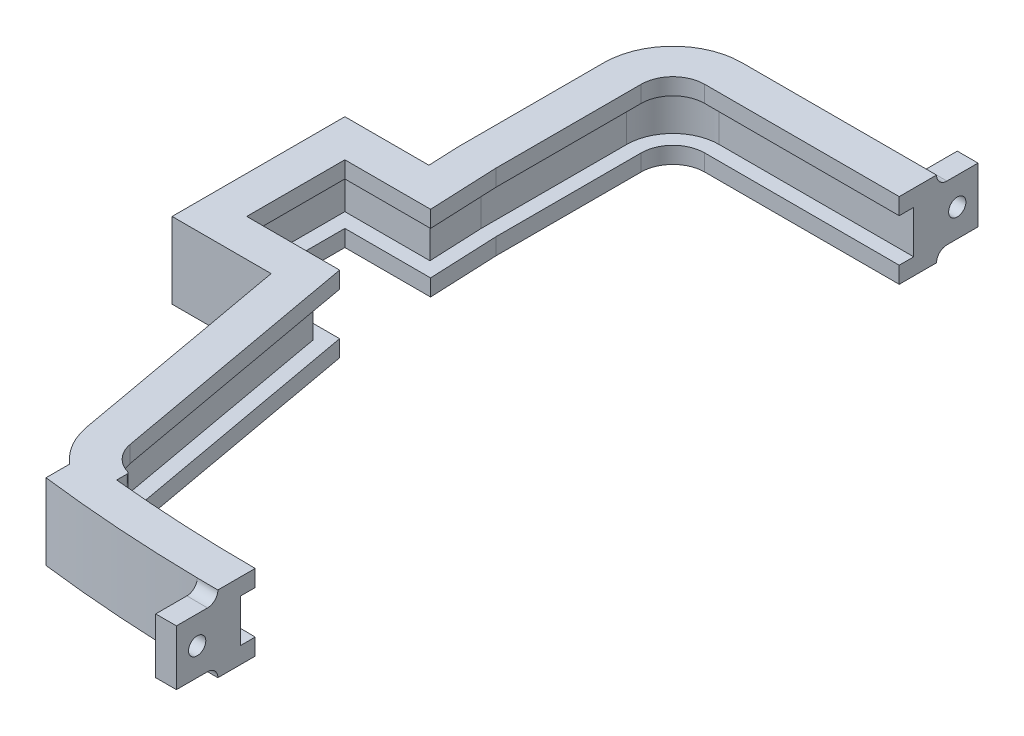
SolidWorks part; units mm, degrees
ref_plane "Front Plane" through (0, 0, 0) normal (0, 0, 1) x (1, 0, 0)
ref_plane "Top Plane" through (0, 0, 0) normal (0, 1, 0) x (1, 0, 0)
ref_plane "Right Plane" through (0, 0, 0) normal (1, 0, 0) x (0, 0, -1)
sketch "Sketch2" plane through (0, 0, 0) normal (0, 1, 0) x (1, 0, 0)
  line L0 (-32.15, 40) -> (-32.15, 19)
  line L1 (-28.15, 44) -> (28.15, 44)
  line L2 (32.15, 40) -> (32.15, 19)
  line L3 (-32.15, 19) -> (-31.6916, 8.5)
  line L6 (-28.15, 50) -> (28.15, 50)
  line L8 (38.15, 40) -> (38.15, 18.8691)
  line L10 (37.9592, 14.5) -> (38.15, 18.8691)
  line L11 (37.9592, 14.5) -> (50.124, 14.5)
  line L12 (50.124, -10.5) -> (50.124, 14.5)
  line L13 (35.7934, -10.5) -> (50.124, -10.5)
  line L14 (35.7934, -10.5) -> (29.9042, -43.0677)
  line L15 (26.5, -52.373) -> (26.5, -48.9417)
  line L16 (-26.5, -52.373) -> (-26.5, -48.9417)
  line L17 (-29.9042, -43.0677) -> (-35.7934, -10.5)
  line L18 (-50.124, -10.5) -> (-35.7934, -10.5)
  line L19 (-50.124, -10.5) -> (-50.124, 14.5)
  line L20 (-50.124, 14.5) -> (-37.9592, 14.5)
  line L21 (-38.15, 18.8691) -> (-37.9592, 14.5)
  line L22 (-38.15, 40) -> (-38.15, 18.8691)
  line L23 (-28.15, 46.7) -> (28.15, 46.7)
  line L24 (-50, 2) -> (50, 2) construction
  line L25 (-44.124, -4.5) -> (-30.7811, -4.5)
  line L26 (30.7811, -4.5) -> (44.124, -4.5)
  line L28 (31.6916, 8.5) -> (44.124, 8.5)
  line L29 (44.124, -4.5) -> (44.124, 8.5)
  line L30 (34.85, 40) -> (34.85, 18.9411)
  line L31 (-20.5, -47) -> (-20.5, -46.0775)
  line L32 (-44.124, -4.5) -> (-44.124, 8.5)
  line L33 (-44.124, 8.5) -> (-31.6916, 8.5)
  line L35 (-20.5, -47) -> (20.5, -47) construction
  line L36 (34.512, 11.2) -> (34.85, 18.9411)
  line L38 (31.6916, 8.5) -> (32.15, 19)
  line L39 (34.512, 11.2) -> (46.824, 11.2)
  line L40 (46.824, -7.2) -> (46.824, 11.2)
  line L41 (33.0366, -7.2) -> (46.824, -7.2)
  line L42 (33.0366, -7.2) -> (26.6569, -42.4804)
  line L43 (23.2, -49.4347) -> (23.2, -47.2089)
  line L44 (-23.2, -49.4347) -> (-23.2, -47.2089)
  line L45 (-26.6569, -42.4804) -> (-33.0366, -7.2)
  line L46 (-46.824, -7.2) -> (-33.0366, -7.2)
  line L47 (-46.824, -7.2) -> (-46.824, 11.2)
  line L48 (-46.824, 11.2) -> (-34.512, 11.2)
  line L49 (-34.85, 18.9411) -> (-34.512, 11.2)
  line L50 (-34.85, 40) -> (-34.85, 18.9411)
  line L51 (-24.5904, -42.1068) -> (-31.2823, -5.1)
  line L52 (-44.724, -5.1) -> (-31.2823, -5.1)
  line L53 (-44.724, -5.1) -> (-44.724, 9.1)
  line L54 (-44.724, 9.1) -> (-32.3183, 9.1)
  line L55 (-21.5547, -45) -> (21.5547, -45) construction
  line L56 (-32.75, 18.9869) -> (-32.3183, 9.1)
  line L57 (-24, -42) -> (24, -42) construction
  line L58 (30.7811, -4.5) -> (24, -42)
  line L59 (-24, -42) -> (-30.7811, -4.5)
  line L60 (20.5, -47) -> (20.5, -46.0775)
  line L61 (-32.75, 40) -> (-32.75, 18.9869)
  line L62 (-28.15, 44.6) -> (28.15, 44.6)
  line L63 (32.75, 40) -> (32.75, 18.9869)
  line L64 (32.3183, 9.1) -> (32.75, 18.9869)
  line L65 (32.3183, 9.1) -> (44.724, 9.1)
  line L66 (44.724, -5.1) -> (44.724, 9.1)
  line L67 (31.2823, -5.1) -> (44.724, -5.1)
  line L68 (31.2823, -5.1) -> (24.5904, -42.1068)
  line L69 (21.1, -47.5435) -> (21.1, -46.0775)
  line L70 (-21.1, -47.5435) -> (-21.1, -46.0775)
  arc A2 (-28.15, 44) -> (-32.15, 40) centre (-28.15, 40) ccw
  arc A3 (32.15, 40) -> (28.15, 44) centre (28.15, 40) ccw
  arc A10 (38.15, 40) -> (28.15, 50) centre (28.15, 40) ccw
  arc A11 (29.9042, -43.0677) -> (26.5, -48.9417) centre (20.0638, -41.2882) cw
  arc A12 (26.5, -48.9417) -> (26.5, -48.9417) centre (26.5, -48.9417) cw
  arc A13 (-26.5, -52.373) -> (26.5, -52.373) centre (0, 162.625) ccw
  arc A14 (-26.5, -48.9417) -> (-26.5, -48.9417) centre (-26.5, -48.9417) ccw
  arc A15 (-29.9042, -43.0677) -> (-26.5, -48.9417) centre (-20.0638, -41.2882) ccw
  arc A16 (-28.15, 50) -> (-38.15, 40) centre (-28.15, 40) ccw
  arc A17 (34.85, 40) -> (28.15, 46.7) centre (28.15, 40) ccw
  arc A18 (26.6569, -42.4804) -> (23.2, -47.2089) centre (20.0638, -41.2882) cw
  arc A19 (23.2, -47.2089) -> (23.2, -47.2089) centre (23.2, -47.2089) cw
  arc A20 (-23.2, -49.4347) -> (23.2, -49.4347) centre (0, 162.625) ccw
  arc A21 (-23.2, -47.2089) -> (-23.2, -47.2089) centre (-23.2, -47.2089) ccw
  arc A22 (-20.5, -47) -> (20.5, -47) centre (0, 162.625) ccw
  arc A23 (-20.5, -46.0775) -> (-21.2128, -45.1197) centre (-21.5, -46.0775) ccw
  arc A24 (-24, -42) -> (-21.2128, -45.1197) centre (-20.0638, -41.2882) ccw
  arc A25 (24, -42) -> (21.2128, -45.1197) centre (20.0638, -41.2882) cw
  arc A26 (20.5, -46.0775) -> (21.2128, -45.1197) centre (21.5, -46.0775) cw
  arc A27 (-26.6569, -42.4804) -> (-23.2, -47.2089) centre (-20.0638, -41.2882) ccw
  arc A28 (-28.15, 46.7) -> (-34.85, 40) centre (-28.15, 40) ccw
  arc A29 (-28.15, 44.6) -> (-32.75, 40) centre (-28.15, 40) ccw
  arc A30 (32.75, 40) -> (28.15, 44.6) centre (28.15, 40) ccw
  arc A31 (24.5904, -42.1068) -> (21.3851, -45.6944) centre (20.0638, -41.2882) cw
  arc A32 (21.1, -46.0775) -> (21.3851, -45.6944) centre (21.5, -46.0775) cw
  arc A33 (-21.1, -47.5435) -> (21.1, -47.5435) centre (0, 162.625) ccw
  arc A34 (-21.1, -46.0775) -> (-21.3851, -45.6944) centre (-21.5, -46.0775) ccw
  arc A35 (-24.5904, -42.1068) -> (-21.3851, -45.6944) centre (-20.0638, -41.2882) ccw
  point P0 (0, 0)
  point P1 (-29.7948, -34.9429)
  point P3 (29.7948, -34.9429)
  point P26 (0, -48)
  point P34 (0, 2)
  point P43 (0, -48)
  point P80 (0, -2)
  point P103 (0, -47)
  point P104 (0, -42)
  dimension "D6" = 177.5
  dimension "D7" = 12.4324
  dimension "D8" = 13
  dimension "D9" = 4
  dimension "D12" = 6.5
  dimension "D18" = 6.5
  dimension "D19" = 6
  dimension "D20" = 42
  dimension "D25" = 0.6
  dimension "D29" = 8
  dimension "D30" = 2
  dimension "D31" = 4
  dimension "D32" = 1
  dimension "D1" = 44
  dimension "D2" = 177.5
  dimension "D4" = 32.15
  dimension "D5" = 32.15
  dimension "D10" = 21
  dimension "D11" = 21
  dimension "D13" = 42
  dimension "D14" = 2
  dimension "D15" = 100.25
  dimension "D16" = 13
  dimension "D17" = 100.25
  dimension "D21" = 100
  dimension "D22" = 48
  dimension "D23" = 12.4324
  dimension "D24" = 2.7
  dimension "D28" = 56.3
  dimension "D33" = 3
  dimension "D34" = 3
  dimension "D35" = 3.1197
  dimension "D36" = 0.9225
  dimension "D37" = 0
extrude "Boss-Extrude1" add sketch "Sketch2" against normal blind 4.5 contours L15 L42 L41 L40 L39 L23 L17 L16 A13 L6 L11 L12 L13 L14 | L23 A28 L50 L49 L48 L47 L46 L45 A27 L44 A20 L43 A18 L42 L41 L40 L39 L36 L30 A17 A35 L51 L52 L53 L54 L56 L61 A29 L62 A30 L63 L64 L65 L66 L67 L68 A31 A32 L69 A33 L70 A34 region at (0, 0, -48.5555) region at (0, 0, -45.3488)
extrude "Cut-Extrude3" cut sketch "Sketch2<6>" against normal blind 2.1 contours L23 A28 L50 L49 L48 L47 L46 L45 A27 L44 A20 L43 A18 L42 L41 L40 L39 L36 L30 A17 A35 L51 L52 L53 L54 L56 L61 A29 L62 A30 L63 L64 L65 L66 L67 L68 A31 A32 L69 A33 L70 A34 | L51 A35 A34 L70 A33 L69 A32 A31 L68 L67 L66 L65 L64 L63 A30 L62 A29 L61 L56 L54 L53 L52 A26 L60 A22 L31 A23 A24 L59 L25 L32 L33 L3 L0 A2 L1 A3 L2 L38 L28 L29 L26 L58 A25 region at (0, 0, -45.3488) region at (-27.8092, 0, 23.5804)
sketch "Sketch2<6>" plane through (0, 0, 0) normal (0, 1, 0) x (1, 0, 0) same geometry as "Sketch2"
extrude "Boss-Extrude3" add sketch "Sketch2<7>" along normal blind 6.5 contours L6 A16 L22 L21 L20 L19 L18 L17 A15 L16 A13 L15 A11 L14 L13 L12 L11 L10 L8 A10 A28 L23 A17 L30 L36 L39 L40 L41 L42 A18 L43 A20 L44 A27 L45 L46 L47 L48 L49 L50 | L23 A28 L50 L49 L48 L47 L46 L45 A27 L44 A20 L43 A18 L42 L41 L40 L39 L36 L30 A17 A35 L51 L52 L53 L54 L56 L61 A29 L62 A30 L63 L64 L65 L66 L67 L68 A31 A32 L69 A33 L70 A34 region at (0, 0, -48.5555) region at (0, 0, -45.3488)
sketch "Sketch2<7>" plane through (0, 0, 0) normal (0, 1, 0) x (1, 0, 0) same geometry as "Sketch2"
extrude "Cut-Extrude4" cut sketch "Sketch2<8>" along normal blind 4.1 contours L14 L13 L12 L11 L6 L25 L32 L33 L3 L0 A2 L1 A3 L2 L38 L28 L29 L26 | L23 A28 L50 L49 L48 L47 L46 L45 A27 L44 A20 L43 A18 L42 L41 L40 L39 L36 L30 A17 A35 L51 L52 L53 L54 L56 L61 A29 L62 A30 L63 L64 L65 L66 L67 L68 A31 A32 L69 A33 L70 A34 region at (0, 0, -45.3488) region at (-27.8092, 0, 23.5804)
sketch "Sketch2<8>" plane through (0, 0, 0) normal (0, 1, 0) x (1, 0, 0) same geometry as "Sketch2"
sketch "Sketch4" plane through (0, 0, 0) normal (1, 0, 0) x (0, 0, -1)
  line L0 (50, -4.5) -> (50, 6.5) construction
  line L1 (50, -3) -> (56, -3)
  line L2 (50, -3) -> (50, 5)
  line L3 (50, 5) -> (56, 5)
  line L4 (56, -3) -> (56, 5)
  line L5 (50, -3) -> (56, 5) construction
  line L6 (50, 5) -> (56, -3) construction
  line L7 (-60, -3) -> (-54, -3)
  line L8 (-60, -3) -> (-60, 5)
  line L9 (-60, 5) -> (-54, 5)
  line L11 (-60, -3) -> (-54, 5) construction
  line L12 (-60, 5) -> (-54, -3) construction
  line L15 (-54, 5) -> (-52, 5)
  line L17 (-54, -3) -> (-52, -3)
  line L18 (-52, 5) -> (-52, -3)
  circle A0 centre (53, 1) radius 1.25
  circle A1 centre (-57, 1) radius 1.25
  point P0 (53, 1)
  point P7 (-57, 1)
  point P9 (50, 1)
  point P26 (-54, 1)
  dimension "D3" = 2.5
  dimension "D6" = 2.5
  dimension "D1" = 6
  dimension "D2" = 8
  dimension "D4" = 6
  dimension "D5" = 8
  dimension "D7" = 1
  dimension "D8" = 52
  dimension "D9" = 1
  dimension "D10" = 2
extrude "Boss-Extrude4" add sketch "Sketch4" along normal blind 3 and the other way blind 3
fillet "Fillet1" radius 1.5 4 edges at (0, -3, -50) (0, 5, -50) (0, -3, 54) (0, 5, 54)
sketch "Sketch5" plane through (0, 0, 0) normal (1, 0, 0) x (0, 0, -1)
  line L1 (-75, -20) -> (75, -20)
  line L2 (-75, -20) -> (-75, 20)
  line L3 (-75, 20) -> (75, 20)
  line L4 (75, -20) -> (75, 20)
  line L5 (-75, -20) -> (75, 20) construction
  line L6 (-75, 20) -> (75, -20) construction
  point P0 (0, 0)
extrude "Cut-Extrude5" cut sketch "Sketch5" along normal through all
